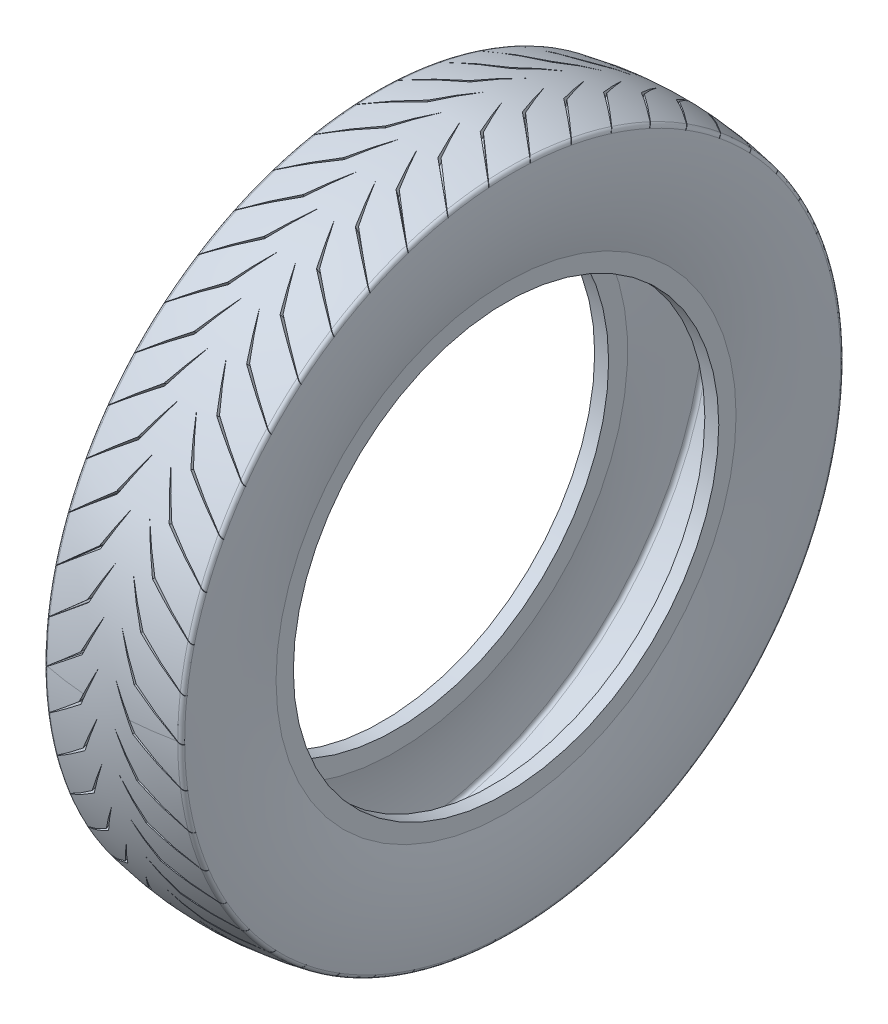
SolidWorks part; units mm, degrees
material "Polyurethane Foam Flexible"
ref_plane "Front Plane" through (0, 0, 0) normal (0, 0, 1) x (1, 0, 0)
ref_plane "Top Plane" through (0, 0, 0) normal (0, 1, 0) x (1, 0, 0)
ref_plane "Right Plane" through (0, 0, 0) normal (1, 0, 0) x (0, 0, -1)
sketch "Sketch1" plane through (0, 0, 0) normal (0, 0, 1) x (1, 0, 0)
  line L0 (0, 0) -> (0, 100.3824) construction
  line L1 (-44.45, 10.3824) -> (-34.45, 10.3824)
  line L2 (0, 60.3824) -> (50, 60.3824) construction
  line L3 (44.45, 10.3824) -> (44.45, 22.7781)
  line L4 (-44.45, 10.3824) -> (-44.45, 22.7781)
  line L5 (34.45, 20.3824) -> (34.45, 23.9918)
  line L7 (-34.45, 20.3824) -> (-34.45, 23.9918)
  line L8 (-34.45, 20.3824) -> (34.45, 20.3824) construction
  line L9 (-34.45, 20.3824) -> (-34.45, 10.3824)
  line L10 (34.45, 20.3824) -> (34.45, 10.3824)
  line L11 (34.45, 10.3824) -> (44.45, 10.3824)
  line L12 (-44.45, 10.3824) -> (44.45, 10.3824) construction
  line L13 (0, 100.3824) -> (0, -142.0176) construction
  line L14 (-120.5248, -142.0176) -> (144.6538, -142.0176) construction
  arc A0 (46.8367, 95.5538) -> (-46.8367, 95.5538) centre (0, -129.187) ccw
  arc A1 (44.45, 22.7781) -> (49.2087, 92.9257) centre (-156.4693, 71.6434) ccw
  arc A2 (-44.45, 22.7781) -> (-49.2087, 92.9257) centre (156.4693, 71.6434) cw
  arc A3 (-34.45, 23.9918) -> (-39.8923, 84.4105) centre (156.4693, 71.6434) cw
  arc A4 (37.4097, 87.172) -> (-37.4097, 87.172) centre (0, -129.187) ccw
  arc A5 (34.45, 23.9918) -> (39.8923, 84.4105) centre (-156.4693, 71.6434) ccw
  arc A6 (44.45, 22.7781) -> (48.9723, 95.0981) centre (-156.4693, 71.6434) ccw construction
  arc A7 (48.9723, 95.0981) -> (-48.9723, 95.0981) centre (0, -129.187) ccw construction
  arc A8 (49.2087, 92.9257) -> (46.8367, 95.5538) centre (46.2247, 92.6169) ccw
  arc A9 (39.7255, 86.7588) -> (-39.7255, 86.7588) centre (0, -129.187) ccw construction
  arc A10 (34.45, 23.9918) -> (39.7255, 86.7588) centre (-156.4693, 71.6434) ccw construction
  arc A11 (37.4097, 87.172) -> (39.8923, 84.4105) centre (36.8986, 84.2159) cw
  arc A12 (-34.45, 23.9918) -> (-39.7255, 86.7588) centre (156.4693, 71.6434) cw construction
  arc A13 (-39.8923, 84.4105) -> (-37.4097, 87.172) centre (-36.8986, 84.2159) cw
  arc A14 (-44.45, 22.7781) -> (-48.9723, 95.0981) centre (156.4693, 71.6434) cw construction
  arc A15 (-49.2087, 92.9257) -> (-46.8367, 95.5538) centre (-46.2247, 92.6169) cw
  point P28 (48.9723, 95.0981)
  dimension "D1" = 152.4
  dimension "D2" = 50
  dimension "D5" = 3
  dimension "D3" = 50
  dimension "D6" = 88.9
  dimension "D7" = 242.4
  dimension "D4" = 10
revolve "Revolve1" add sketch "Sketch1" angle 360 about L14
ref_plane "Plane1" through (0, 0, 242.316) normal (0, 0, 1) x (1, 0, 0)
sketch "Sketch2" plane through (0, 0, 242.316) normal (0, 0, 1) x (1, 0, 0)
  line L0 (-46.8367, -142.0176) -> (46.8367, -142.0176) construction
  line L1 (-46.8367, 95.5538) -> (-46.8367, -379.589) construction
  line L2 (46.8367, 95.5538) -> (46.8367, -379.589) construction
  line L3 (-49.2087, -144.4213) -> (-18.5947, -119.5467)
  line L4 (-49.2087, 92.9257) -> (-49.2087, -376.9609) construction
  line L5 (-18.5947, -119.5467) -> (-6.1811, -91.5426)
  line L6 (-6.1811, -91.5426) -> (-19.9088, -118.5606)
  line L7 (-19.9088, -118.5606) -> (-49.2087, -144.2086)
  line L8 (0, -142.0176) -> (0, -84.3034) construction
  line L9 (19.9088, -118.5606) -> (49.2087, -144.2086)
  line L10 (6.1811, -91.5426) -> (19.9088, -118.5606)
  line L11 (18.5947, -119.5467) -> (6.1811, -91.5426)
  line L12 (49.2087, -144.4213) -> (18.5947, -119.5467)
  arc A0 (-49.2087, -144.2086) -> (-49.2087, -144.4213) centre (-49.1156, -144.3149) ccw
  arc A1 (49.2087, -144.2086) -> (49.2087, -144.4213) centre (49.1156, -144.3149) cw
extrude "Cut-Extrude1" cut sketch "Sketch2" against normal blind 7.62
ref_axis "Axis1" through (509.2704, -142.0176, 0) along (-1, 0, 0)
pattern_circular "CirPattern1" count 50 over 360 about axis through (509.2704, -142.0176, 0) along (-1, 0, 0) of "Cut-Extrude1"
